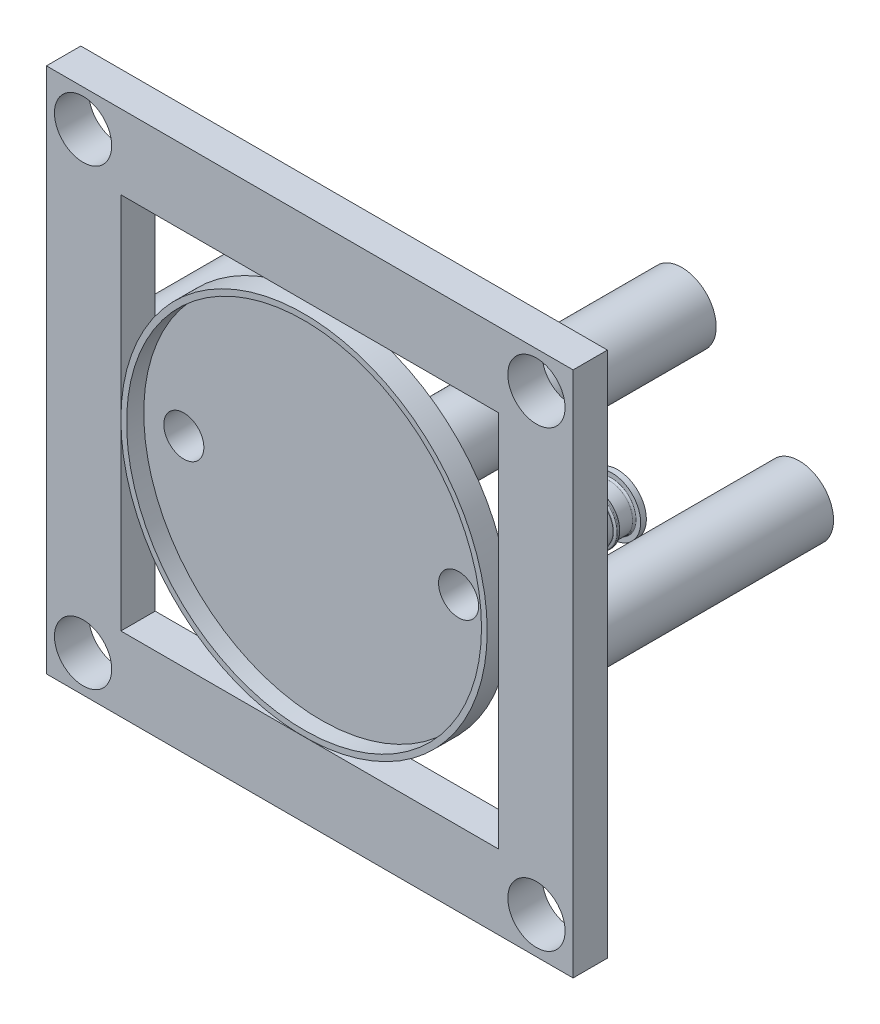
SolidWorks part; units mm, degrees
ref_plane "Piano frontale" through (0, 0, 0) normal (0, 0, 1) x (1, 0, 0)
ref_plane "Piano superiore" through (0, 0, 0) normal (0, 1, 0) x (1, 0, 0)
ref_plane "Piano destro" through (0, 0, 0) normal (1, 0, 0) x (0, 0, -1)
sketch "Schizzo1" plane through (0, 0, 0) normal (0, 0, 1) x (1, 0, 0)
  circle A0 centre (0, 0) radius 16
  circle A1 centre (0, 0) radius 15.5
  dimension "D1" = 32
  dimension "D2" = 31
extrude "Estrusione-Estrusione1" add sketch "Schizzo1" against normal blind 1.5
sketch "Schizzo2" plane through (0, 0, -1.5) normal (0, 0, -1) x (-1, 0, 0)
  circle A0 centre (0, 0) radius 16
extrude "Estrusione-Estrusione2" add sketch "Schizzo2" along normal blind 0.5
sketch "Schizzo6" plane through (0, 0, -2) normal (0, 0, -1) x (-1, 0, 0)
  circle A0 centre (12, 0) radius 3.5
  dimension "D1" = 7
  dimension "D2" = 12
extrude "Estrusione-Estrusione4" add sketch "Schizzo6" along normal blind 0.5 contours A0
sketch "Schizzo7" plane through (0, 0, -2.5) normal (0, 0, -1) x (-1, 0, 0)
  circle A0 centre (12, 0) radius 2
  dimension "D1" = 4
extrude "Estrusione-Estrusione5" add sketch "Schizzo7" along normal blind 10.5
sketch "Schizzo8" plane through (0, 0, -13) normal (0, 0, -1) x (-1, 0, 0)
  circle A0 centre (12, 0) radius 2.25
  dimension "D1" = 4.5
extrude "Estrusione-Estrusione6" add sketch "Schizzo8" along normal blind 0.4
sketch "Schizzo9" plane through (0, 0, -13.4) normal (0, 0, -1) x (-1, 0, 0)
  circle A0 centre (12, 0) radius 2 construction
  circle A1 centre (12, 0) radius 2
extrude "Estrusione-Estrusione7" add sketch "Schizzo9" along normal blind 2
sketch "Schizzo10" plane through (0, 0, -15.4) normal (0, 0, -1) x (-1, 0, 0)
  circle A0 centre (12, 0) radius 2.5
  dimension "D1" = 5
extrude "Estrusione-Estrusione8" add sketch "Schizzo10" against normal blind 0.5
sketch "Schizzo11" plane through (0, 0, -15.4) normal (0, 0, -1) x (-1, 0, 0)
  circle A0 centre (12, 0) radius 1.75
  dimension "D1" = 3.5
extrude "Taglio-Estrusione5" cut sketch "Schizzo11" against normal up to next contours A0
fillet "Raccordo2" radius 0.2 1 edges at (-14.25, 0, -13) second distance 0.1 first distance on face at (-14, 0, -13)
fillet "Raccordo3" radius 0.2 1 edges at (-14.25, 0, -13.4) second distance 0.1
fillet "Raccordo4" radius 0.2 1 edges at (-14, 0, -14.9) second distance 0.1 first distance on face at (-14, 0, -13.4)
fillet "Raccordo5" radius 0.2 1 edges at (-14, 0, -2.5) second distance 0.1 first distance on face at (-14, 0, -2.5)
fillet "Raccordo6" radius 0.2 1 edges at (-15.5, 0, -2) second distance 0.1 first distance on face at (-15.5, 0, -2)
mirror "Specchia1" about plane through (0, 0, 0) normal (1, 0, 0) of "Raccordo6", "Raccordo5", "Raccordo4", "Raccordo3", "Raccordo2", "Taglio-Estrusione5", "Estrusione-Estrusione8", "Estrusione-Estrusione7", "Estrusione-Estrusione6", "Estrusione-Estrusione5", "Estrusione-Estrusione4"
sketch "Schizzo12" plane through (0, 0, -2) normal (0, 0, -1) x (-1, 0, 0)
  circle A0 centre (0, 0) radius 6
  dimension "D1" = 12
extrude "Estrusione-Estrusione9" add sketch "Schizzo12" along normal blind 1
sketch "Schizzo13" plane through (0, 0, -3) normal (0, 0, -1) x (-1, 0, 0)
  circle A0 centre (0, 0) radius 3
  dimension "D1" = 6
extrude "Estrusione-Estrusione10" add sketch "Schizzo13" along normal blind 30
sketch "Schizzo17" plane through (0, 0, -2) normal (0, 0, -1) x (-1, 0, 0)
  line L1 (-23, -23) -> (23, -23)
  line L2 (-23, -23) -> (-23, 23)
  line L3 (-23, 23) -> (23, 23)
  line L4 (23, -23) -> (23, 23)
  line L5 (-23, -23) -> (23, 23) construction
  line L6 (-23, 23) -> (23, -23) construction
  line L7 (-16.5, -16.5) -> (16.5, -16.5)
  line L8 (-16.5, -16.5) -> (-16.5, 16.5)
  line L9 (-16.5, 16.5) -> (16.5, 16.5)
  line L10 (16.5, -16.5) -> (16.5, 16.5)
  line L11 (-16.5, -16.5) -> (16.5, 16.5) construction
  line L12 (-16.5, 16.5) -> (16.5, -16.5) construction
  point P0 (0, 0)
  point P7 (0, 0)
  dimension "D1" = 46
  dimension "D2" = 46
  dimension "D3" = 33
  dimension "D4" = 33
extrude "Estrusione-Estrusione12" add sketch "Schizzo17" against normal blind 1.5 and the other way blind 1.5 separate body
sketch "Schizzo18" plane through (0, 0, -3.5) normal (0, 0, -1) x (-1, 0, 0)
  circle A0 centre (0, 0) radius 28
  dimension "D1" = 56
hole_wizard "Foro per Vite M1-1" positions "Schizzo19" profile "Schizzo20" hole size "M1" standard "ISO" end condition up to next
sketch "Schizzo19" plane through (0, 0, -3.5) normal (0, 0, -1) x (-1, 0, 0)
  circle A0 centre (0, 0) radius 28 construction
  point P0 (-19.798, 19.8)
  dimension "D1" = 19.8
sketch "Schizzo20" plane through (19.798, 19.8, -3.5) normal (1, 0, 0) x (0, 1, 0)
  line L0 (0, 0) -> (0, 3.001)
  line L1 (0, 3.001) -> (2.5, 3.001)
  line L2 (2.5, 3.001) -> (2.5, 0)
  line L5 (2.5, 0) -> (0, 0)
  line L11 (0, -6.35) -> (0, 107.95) construction
  dimension "Thru Hole Dia." = 5
  dimension "Thru Hole Depth" = 3.001
pattern_circular "RipetizioneCircolare1" count 4 over 360 about axis through (0, 0, -33) along (0, 0, -1) of "Foro per Vite M1-1"
sketch "Schizzo21" plane through (0, 0, -3.5) normal (0, 0, -1) x (-1, 0, 0)
  line L0 (-16.5, 16.5) -> (-16.5, -16.5) construction
  circle A0 centre (-19.75, 0) radius 3
  dimension "D1" = 6
  dimension "D2" = 3.25
extrude "Estrusione-Estrusione13" add sketch "Schizzo21" along normal blind 20
fillet "Raccordo7" radius 0.1 1 edges at (22.75, 0, -3.5)
mirror "Specchia2" about plane through (0, 0, 0) normal (1, 0, 0) of "Raccordo7", "Estrusione-Estrusione13"
